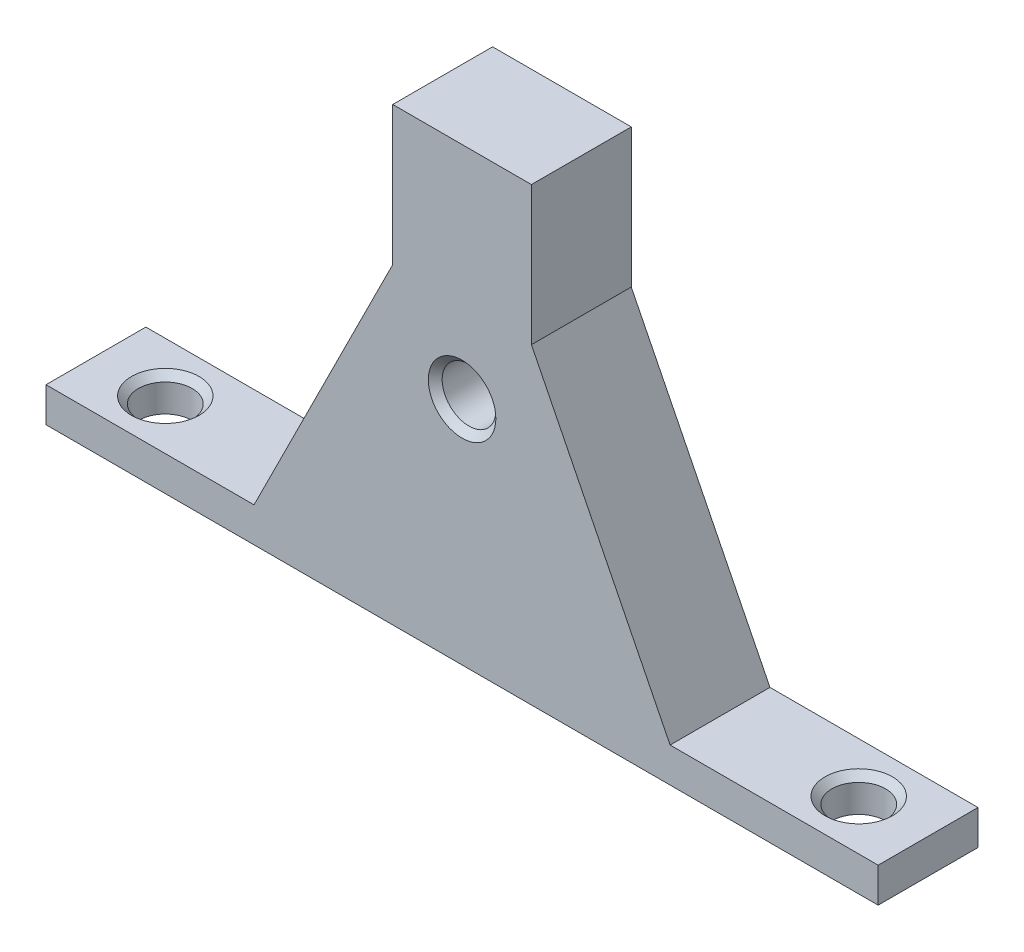
SolidWorks part; units mm, degrees
ref_plane "Front Plane" through (0, 0, 0) normal (0, 0, 1) x (1, 0, 0)
ref_plane "Top Plane" through (0, 0, 0) normal (0, 1, 0) x (1, 0, 0)
ref_plane "Right Plane" through (0, 0, 0) normal (1, 0, 0) x (0, 0, -1)
sketch "Sketch1" plane through (0, 0, 0) normal (0, 1, 0) x (1, 0, 0)
  line L1 (-38.1, -4.572) -> (38.1, -4.572)
  line L2 (-38.1, -4.572) -> (-38.1, 4.572)
  line L3 (-38.1, 4.572) -> (38.1, 4.572)
  line L4 (38.1, -4.572) -> (38.1, 4.572)
  line L5 (-38.1, -4.572) -> (38.1, 4.572) construction
  line L6 (-38.1, 4.572) -> (38.1, -4.572) construction
  point P0 (0, 0)
  dimension "D1" = 76.2
  dimension "D2" = 9.144
extrude "Boss-Extrude1" add sketch "Sketch1" along normal blind 3.175
hole_wizard "#8 Clearance Hole1" positions "Sketch2" profile "Sketch3" hole size "#8" standard "ANSI Inch" end condition through all
sketch "Sketch2" plane through (0, 3.175, 0) normal (0, 1, 0) x (1, 0, 0)
  point P0 (-31.75, 0)
  point P2 (31.75, 0)
  dimension "D1" = 31.75
  dimension "D2" = 31.75
sketch "Sketch3" plane through (-31.75, 3.175, 0) normal (1, 0, 0) x (0, 0, 1)
  line L0 (0, 0) -> (0, 3.175)
  line L1 (0, 3.175) -> (2.4574, 3.175)
  line L2 (2.4574, 3.175) -> (2.4574, 0.635)
  line L3 (2.4574, 0.635) -> (3.0924, 0)
  line L5 (3.0924, 0) -> (0, 0)
  line L6 (-2.4574, 0.635) -> (-3.0924, 0) construction
  line L11 (0, -6.35) -> (0, 107.95) construction
  dimension "Thru Hole Dia." = 4.9149
  dimension "Thru Hole Depth" = 3.175
  dimension "Near C'Sink Dia." = 6.1849
  dimension "Near C'Sink Angle" = 90
sketch "Sketch4" plane through (0, 0, 4.572) normal (0, 0, 1) x (1, 0, 0)
  line L0 (-19.05, 3.175) -> (-6.35, 28.575)
  line L1 (-6.35, 28.575) -> (-6.35, 41.275)
  line L2 (-6.35, 41.275) -> (6.35, 41.275)
  line L3 (0, 41.275) -> (0, 3.175)
  line L4 (-38.1, 0) -> (38.1, 0)
  line L5 (38.1, 0) -> (38.1, 3.175)
  line L6 (38.1, 3.175) -> (-38.1, 3.175)
  line L7 (-38.1, 3.175) -> (-38.1, 0)
  line L8 (-38.1, 0) -> (38.1, 0)
  line L9 (38.1, 0) -> (38.1, 3.175)
  line L10 (38.1, 3.175) -> (-38.1, 3.175)
  line L11 (-38.1, 3.175) -> (-38.1, 0)
  line L12 (0, 3.175) -> (-19.05, 3.175)
  line L13 (6.35, 28.575) -> (6.35, 41.275)
  line L14 (19.05, 3.175) -> (6.35, 28.575)
  line M10 (38.1, 3.175) -> (-38.1, 3.175)
  dimension "D2" = 38.1
  dimension "D3" = 6.35
  dimension "D4" = 19.05
  dimension "D5" = 12.7
  dimension "D1" = 0
extrude "Boss-Extrude2" add sketch "Sketch4" against normal up to surface (9.144 mm away) contours L3 L2 L1 L0 M10 | L10 L14 L13 L2 L3 region at (-6.1383, 17.9917, 4.572) region at (6.1383, 17.9917, 4.572) up to face at (0, 1.5875, -4.572)
hole_wizard "#8 Clearance Hole2" positions "Sketch5" profile "Sketch6" hole size "#8" standard "ANSI Inch" end condition through all
sketch "Sketch5" plane through (0, 0, 4.572) normal (0, 0, 1) x (1, 0, 0)
  line L0 (-6.35, 41.275) -> (6.35, 41.275) construction
  point P0 (0, 21.082)
  dimension "D1" = 20.193
sketch "Sketch6" plane through (0, 21.082, 4.572) normal (1, 0, 0) x (0, -1, 0)
  line L0 (0, 0) -> (0, 9.144)
  line L1 (0, 9.144) -> (2.4574, 9.144)
  line L2 (2.4574, 9.144) -> (2.4574, 0.635)
  line L3 (2.4574, 0.635) -> (3.0924, 0)
  line L5 (3.0924, 0) -> (0, 0)
  line L6 (-2.4574, 0.635) -> (-3.0924, 0) construction
  line L11 (0, -6.35) -> (0, 107.95) construction
  dimension "Thru Hole Dia." = 4.9149
  dimension "Thru Hole Depth" = 9.144
  dimension "Near C'Sink Dia." = 6.1849
  dimension "Near C'Sink Angle" = 90
